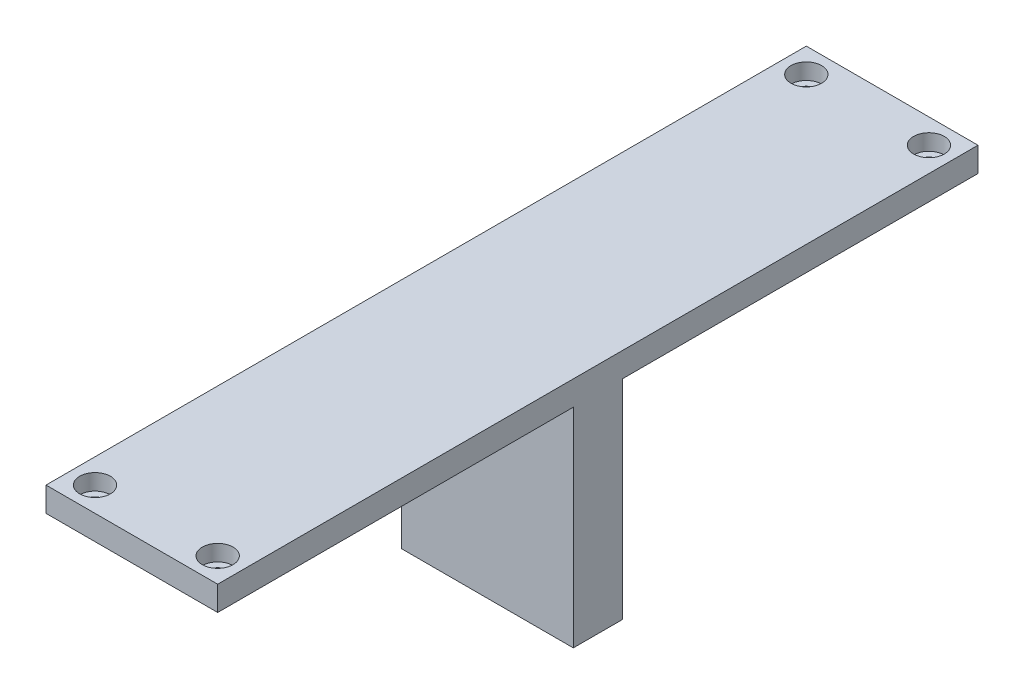
SolidWorks part; units mm, degrees
material "6061 Alloy"
ref_plane "Front Plane" through (0, 0, 0) normal (0, 0, 1) x (1, 0, 0)
ref_plane "Top Plane" through (0, 0, 0) normal (0, 1, 0) x (1, 0, 0)
ref_plane "Right Plane" through (0, 0, 0) normal (1, 0, 0) x (0, 0, -1)
sketch "Sketch1" plane through (0, 0, 0) normal (0, 1, 0) x (1, 0, 0)
  line L1 (-22.225, -98.425) -> (22.225, -98.425)
  line L2 (-22.225, -98.425) -> (-22.225, 98.425)
  line L3 (-22.225, 98.425) -> (22.225, 98.425)
  line L4 (22.225, -98.425) -> (22.225, 98.425)
  line L5 (-22.225, -98.425) -> (22.225, 98.425) construction
  line L6 (-22.225, 98.425) -> (22.225, -98.425) construction
  point P0 (0, 0)
  dimension "D1" = 196.85
  dimension "D2" = 44.45
extrude "Boss-Extrude1" add sketch "Sketch1" along normal blind 6.35
sketch "Sketch2" plane through (0, 0, 0) normal (0, -1, 0) x (-1, 0, 0)
  line L0 (-22.225, -98.425) -> (-22.225, 98.425) construction
  line L1 (22.225, 6.35) -> (-22.225, 6.35)
  line L2 (22.225, 6.35) -> (22.225, -6.35)
  line L3 (22.225, -6.35) -> (-22.225, -6.35)
  line L4 (-22.225, 6.35) -> (-22.225, -6.35)
  line L5 (22.225, 6.35) -> (-22.225, -6.35) construction
  line L6 (22.225, -6.35) -> (-22.225, 6.35) construction
  point P0 (0, 0)
  dimension "D1" = 12.7
extrude "Boss-Extrude2" add sketch "Sketch2" along normal blind 53.975
hole_wizard "CBORE for #8 Socket Head Cap Screw1" positions "Sketch4" profile "Sketch5" counterbore size "#8" standard "ANSI Inch" end condition up to next
sketch "Sketch4" plane through (0, 6.35, 0) normal (0, 1, 0) x (1, 0, 0)
  line L0 (-22.225, 98.425) -> (-22.225, -98.425) construction
  line L1 (-22.225, -98.425) -> (22.225, -98.425) construction
  line L2 (22.225, 98.425) -> (-22.225, 98.425) construction
  line L3 (22.225, -98.425) -> (22.225, 98.425) construction
  point P0 (-15.875, -92.075)
  point P2 (15.875, -92.075)
  point P4 (15.875, 92.075)
  point P6 (-15.875, 92.075)
  dimension "D1" = 6.35
  dimension "D2" = 6.35
  dimension "D3" = 6.35
  dimension "D4" = 6.35
  dimension "D5" = 6.35
  dimension "D6" = 6.35
  dimension "D7" = 6.35
  dimension "D8" = 6.35
sketch "Sketch5" plane through (-15.875, 6.35, 92.075) normal (1, 0, 0) x (0, 0, 1)
  line L0 (0, 0) -> (0, 6.35)
  line L1 (0, 6.35) -> (2.1526, 6.35)
  line L3 (2.1526, 6.35) -> (2.1527, 4.1656)
  line L4 (2.1527, 4.1656) -> (3.9687, 4.1656)
  line L5 (3.9687, 4.1656) -> (3.9687, 0)
  line L7 (3.9687, 0) -> (0, 0)
  line L11 (0, -6.35) -> (0, 107.95) construction
  dimension "Thru Hole Dia." = 4.3053
  dimension "Thru Hole Depth" = 6.35
  dimension "C'Bore Dia." = 7.9375
  dimension "C'Bore Depth" = 4.1656
